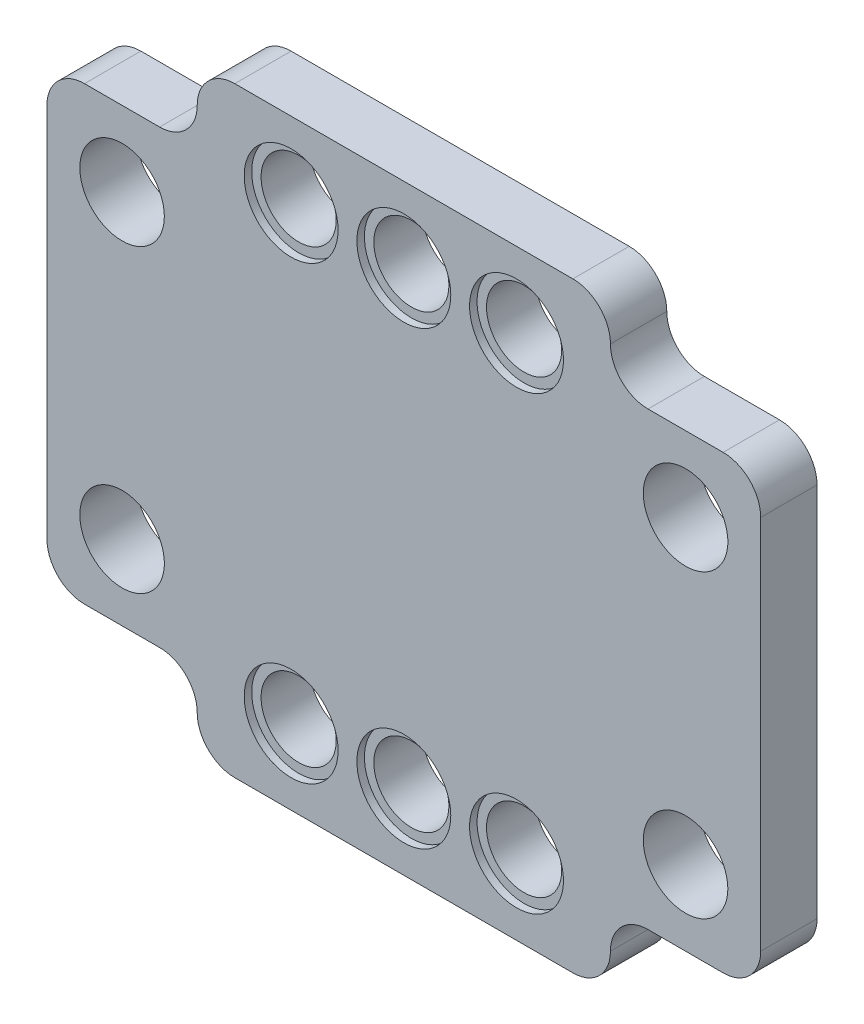
SolidWorks part; units mm, degrees
ref_plane "Plan de face" through (0, 0, 0) normal (0, 0, 1) x (1, 0, 0)
ref_plane "Plan de dessus" through (0, 0, 0) normal (0, 1, 0) x (1, 0, 0)
ref_plane "Plan de droite" through (0, 0, 0) normal (1, 0, 0) x (0, 0, -1)
sketch "Esquisse2" plane through (0, 0, 0) normal (0, 0, 1) x (1, 0, 0)
  line L1 (0, 0) -> (38, 0)
  line L2 (0, 0) -> (0, 32)
  line L3 (0, 32) -> (38, 32)
  line L4 (38, 0) -> (38, 32)
  dimension "D1" = 38
  dimension "D2" = 32
extrude "Boss.-Extru.1" add sketch "Esquisse2" along normal blind 3
sketch "Esquisse3" plane through (0, 0, 3) normal (0, 0, 1) x (1, 0, 0)
  line L0 (19, 0) -> (19, 32) construction
  line L1 (0, 0) -> (38, 0) construction
  line L2 (38, 32) -> (0, 32) construction
  line L3 (0, 16) -> (38, 16) construction
  line L4 (0, 32) -> (0, 0) construction
  line L5 (38, 0) -> (38, 32) construction
  line L6 (13, 28) -> (19, 28) construction
  line L7 (13, 4) -> (19, 4) construction
  circle A0 centre (19, 28) radius 2
  circle A1 centre (13, 28) radius 2
  circle A2 centre (25, 28) radius 2
  circle A3 centre (25, 4) radius 2
  circle A4 centre (13, 4) radius 2
  circle A5 centre (19, 4) radius 2
  circle A6 centre (4, 24) radius 2.25
  circle A7 centre (4, 8) radius 2.25
  circle A8 centre (34, 8) radius 2.25
  circle A9 centre (34, 24) radius 2.25
  dimension "D1" = 4
  dimension "D2" = 24
  dimension "D3" = 6
  dimension "D4" = 4.5
  dimension "D5" = 16
  dimension "D6" = 30
extrude "Enlèv. mat.-Extru.1" cut sketch "Esquisse3" against normal through all both and the other way through all
sketch "Esquisse4" plane through (0, 0, 3) normal (0, 0, 1) x (1, 0, 0)
  circle A0 centre (13, 4) radius 2.5
  circle A1 centre (19, 4) radius 2.5
  circle A2 centre (25, 4) radius 2.5
  circle A3 centre (25, 28) radius 2.5
  circle A4 centre (19, 28) radius 2.5
  circle A5 centre (13, 28) radius 2.5
  dimension "D1" = 5
extrude "Enlèv. mat.-Extru.2" cut sketch "Esquisse4" against normal blind 0.4
sketch "Esquisse5" plane through (0, 0, 3) normal (0, 0, 1) x (1, 0, 0)
  line L0 (19, 32) -> (19, 0) construction
  line L1 (0, 32) -> (8, 32)
  line L2 (0, 32) -> (0, 28)
  line L3 (0, 28) -> (8, 28)
  line L4 (8, 32) -> (8, 28)
  line L5 (38, 32) -> (0, 32) construction
  line L6 (0, 0) -> (38, 0) construction
  line L7 (38, 16) -> (0, 16) construction
  line L8 (38, 0) -> (38, 32) construction
  line L9 (0, 32) -> (0, 0) construction
  line L10 (30, 32) -> (30, 28)
  line L11 (38, 28) -> (30, 28)
  line L12 (38, 32) -> (38, 28)
  line L13 (38, 32) -> (30, 32)
  line L14 (38, 0) -> (30, 0)
  line L15 (38, 0) -> (38, 4)
  line L16 (38, 4) -> (30, 4)
  line L17 (30, 0) -> (30, 4)
  line L18 (8, 0) -> (8, 4)
  line L19 (0, 4) -> (8, 4)
  line L20 (0, 0) -> (0, 4)
  line L21 (0, 0) -> (8, 0)
  dimension "D1" = 4
  dimension "D2" = 8
extrude "Enlèv. mat.-Extru.3" cut sketch "Esquisse5" against normal through all both and the other way through all
fillet "Congé1" radius 2 12 edges at (30, 32, 1.5) (30, 28, 1.5) (38, 28, 1.5) (38, 4, 1.5) (30, 4, 1.5) (30, 0, 1.5) (8, 0, 1.5) (8, 4, 1.5) (0, 4, 1.5) (0, 28, 1.5) (8, 32, 1.5) (8, 28, 1.5)
